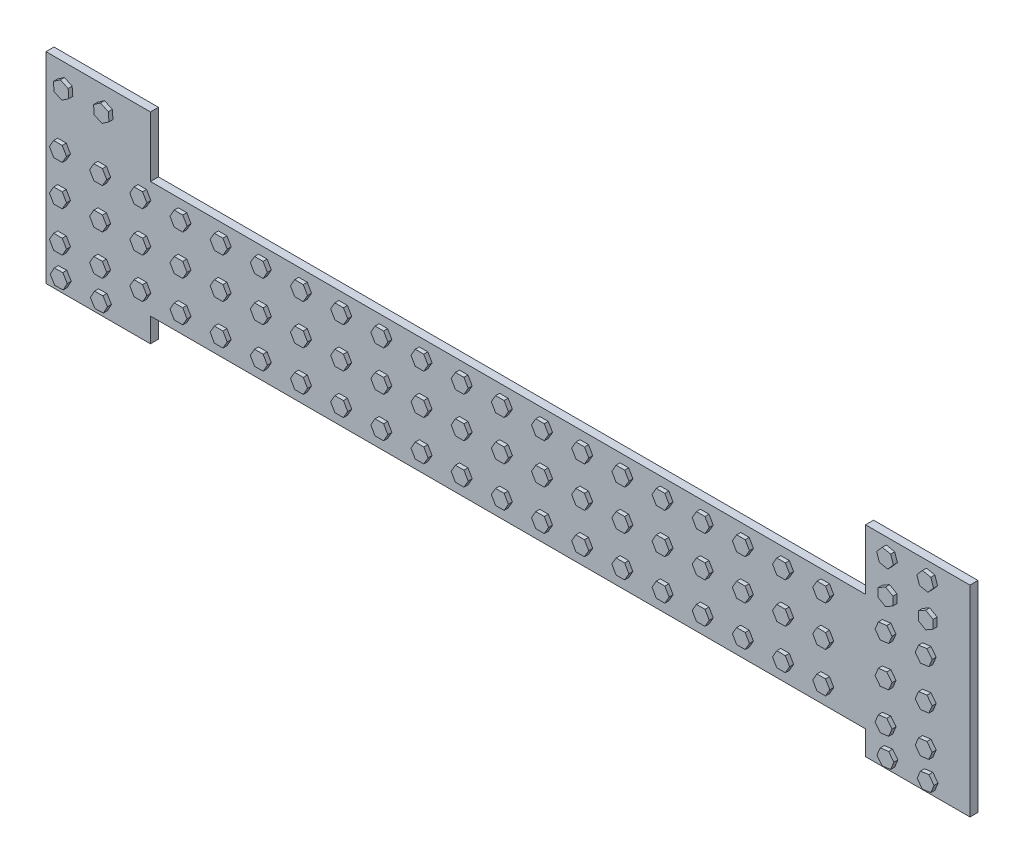
SolidWorks part; units mm, degrees
ref_plane "Front Plane" through (0, 0, 0) normal (0, 0, 1) x (1, 0, 0)
ref_plane "Top Plane" through (0, 0, 0) normal (0, 1, 0) x (1, 0, 0)
ref_plane "Right Plane" through (0, 0, 0) normal (1, 0, 0) x (0, 0, -1)
sketch "Sketch1" plane through (0, 0, 0) normal (0, 0, 1) x (1, 0, 0)
  line L0 (-145.1185, -8.2618) -> (-119.1185, -8.2618)
  line L4 (58.8815, -8.2618) -> (84.8815, -8.2618)
  line L5 (84.8815, -8.2618) -> (84.8815, 41.7382)
  line L7 (-145.1185, 41.7382) -> (-145.1185, -8.2618)
  line L8 (-119.1185, -8.2618) -> (-119.1185, -2.2618)
  line L9 (-119.1185, -2.2618) -> (58.8815, -2.2618)
  line L10 (58.8815, -2.2618) -> (58.8815, -8.2618)
  line L11 (-145.1185, 41.7382) -> (-119.1185, 41.7382)
  line L12 (-119.1185, 41.7382) -> (-119.1185, 26.7382)
  line L13 (-119.1185, 26.7382) -> (58.8815, 26.7382)
  line L14 (58.8815, 26.7382) -> (58.8815, 41.7382)
  line L15 (58.8815, 41.7382) -> (84.8815, 41.7382)
  dimension "D1" = 230
  dimension "D2" = 26
  dimension "D3" = 6
  dimension "D4" = 50
  dimension "D5" = 15
extrude "Boss-Extrude1" add sketch "Sketch1" along normal blind 3
sketch "Sketch2" plane through (0, 0, 3) normal (0, 0, 1) x (1, 0, 0)
  line L0 (-130.1882, 34.2187) -> (-128.4427, 35.4302)
  line L1 (-140.1882, 34.2187) -> (-138.4427, 35.4302)
  line L2 (-138.4427, 35.4302) -> (-138.6192, 37.5475)
  line L3 (-138.6192, 37.5475) -> (-140.541, 38.4533)
  line L4 (-140.541, 38.4533) -> (-142.2865, 37.2419)
  line L5 (-142.2865, 37.2419) -> (-142.11, 35.1246)
  line L6 (-142.11, 35.1246) -> (-140.1882, 34.2187)
  line L13 (-139.8304, -6.4856) -> (-138.8246, -4.6141)
  line L14 (-138.8246, -4.6141) -> (-139.9425, -2.8073)
  line L15 (-139.9425, -2.8073) -> (-142.0662, -2.872)
  line L16 (-142.0662, -2.872) -> (-143.072, -4.7435)
  line L17 (-143.072, -4.7435) -> (-141.9541, -6.5503)
  line L18 (-141.9541, -6.5503) -> (-139.8304, -6.4856)
  line L19 (-139.0172, 2.7003) -> (-140.0796, 4.5403)
  line L20 (-140.0796, 4.5403) -> (-142.2042, 4.5403)
  line L21 (-142.2042, 4.5403) -> (-143.2665, 2.7003)
  line L22 (-143.2665, 2.7003) -> (-142.2042, 0.8603)
  line L23 (-142.2042, 0.8603) -> (-140.0796, 0.8603)
  line L24 (-140.0796, 0.8603) -> (-139.0172, 2.7003)
  line L25 (66.1321, -6.8908) -> (66.939, -4.9253)
  line L26 (66.939, -4.9253) -> (65.6403, -3.2438)
  line L27 (65.6403, -3.2438) -> (63.5347, -3.5277)
  line L28 (63.5347, -3.5277) -> (62.7278, -5.4932)
  line L29 (62.7278, -5.4932) -> (64.0265, -7.1747)
  line L30 (64.0265, -7.1747) -> (66.1321, -6.8908)
  line L31 (65.6558, 0.0237) -> (66.4709, 1.9858)
  line L32 (66.4709, 1.9858) -> (65.1792, 3.6727)
  line L33 (65.1792, 3.6727) -> (63.0724, 3.3976)
  line L34 (63.0724, 3.3976) -> (62.2573, 1.4355)
  line L35 (62.2573, 1.4355) -> (63.549, -0.2515)
  line L36 (63.549, -0.2515) -> (65.6558, 0.0237)
  line L37 (65.4081, 35.9472) -> (66.8177, 37.5368)
  line L38 (66.8177, 37.5368) -> (66.1458, 39.5524)
  line L39 (66.1458, 39.5524) -> (64.0643, 39.9784)
  line L40 (64.0643, 39.9784) -> (62.6547, 38.3887)
  line L41 (62.6547, 38.3887) -> (63.3266, 36.3731)
  line L42 (63.3266, 36.3731) -> (65.4081, 35.9472)
  line L43 (64.8685, 27.5796) -> (66.7085, 28.6419)
  line L44 (66.7085, 28.6419) -> (66.7085, 30.7665)
  line L45 (66.7085, 30.7665) -> (64.8685, 31.8289)
  line L46 (64.8685, 31.8289) -> (63.0285, 30.7665)
  line L47 (63.0285, 30.7665) -> (63.0285, 28.6419)
  line L48 (63.0285, 28.6419) -> (64.8685, 27.5796)
  line L49 (-128.4427, 35.4302) -> (-128.6192, 37.5475)
  line L50 (-128.6192, 37.5475) -> (-130.541, 38.4533)
  line L51 (-130.541, 38.4533) -> (-132.2865, 37.2419)
  line L52 (-132.2865, 37.2419) -> (-132.11, 35.1246)
  line L53 (-132.11, 35.1246) -> (-130.1882, 34.2187)
  line L60 (-129.8304, -6.4856) -> (-128.8246, -4.6141)
  line L61 (-128.8246, -4.6141) -> (-129.9425, -2.8073)
  line L62 (-129.9425, -2.8073) -> (-132.0662, -2.872)
  line L63 (-132.0662, -2.872) -> (-133.072, -4.7435)
  line L64 (-133.072, -4.7435) -> (-131.9541, -6.5503)
  line L65 (-131.9541, -6.5503) -> (-129.8304, -6.4856)
  line L66 (76.1321, -6.8908) -> (76.939, -4.9253)
  line L67 (76.939, -4.9253) -> (75.6403, -3.2438)
  line L68 (75.6403, -3.2438) -> (73.5347, -3.5277)
  line L69 (73.5347, -3.5277) -> (72.7278, -5.4932)
  line L70 (72.7278, -5.4932) -> (74.0265, -7.1747)
  line L71 (74.0265, -7.1747) -> (76.1321, -6.8908)
  line L72 (75.6558, 0.0237) -> (76.4709, 1.9858)
  line L73 (76.4709, 1.9858) -> (75.1792, 3.6727)
  line L74 (75.1792, 3.6727) -> (73.0724, 3.3976)
  line L75 (73.0724, 3.3976) -> (72.2573, 1.4355)
  line L76 (72.2573, 1.4355) -> (73.549, -0.2515)
  line L77 (73.549, -0.2515) -> (75.6558, 0.0237)
  line L78 (75.4081, 35.9472) -> (76.8177, 37.5368)
  line L79 (76.8177, 37.5368) -> (76.1458, 39.5524)
  line L80 (76.1458, 39.5524) -> (74.0643, 39.9784)
  line L81 (74.0643, 39.9784) -> (72.6547, 38.3887)
  line L82 (72.6547, 38.3887) -> (73.3266, 36.3731)
  line L83 (73.3266, 36.3731) -> (75.4081, 35.9472)
  line L84 (74.8685, 27.5796) -> (76.7085, 28.6419)
  line L85 (76.7085, 28.6419) -> (76.7085, 30.7665)
  line L86 (76.7085, 30.7665) -> (74.8685, 31.8289)
  line L87 (74.8685, 31.8289) -> (73.0285, 30.7665)
  line L88 (73.0285, 30.7665) -> (73.0285, 28.6419)
  line L89 (73.0285, 28.6419) -> (74.8685, 27.5796)
  line L90 (-129.0172, 2.7003) -> (-130.0796, 4.5403)
  line L91 (-130.0796, 4.5403) -> (-132.2042, 4.5403)
  line L92 (-132.2042, 4.5403) -> (-133.2665, 2.7003)
  line L93 (-133.2665, 2.7003) -> (-132.2042, 0.8603)
  line L94 (-132.2042, 0.8603) -> (-130.0796, 0.8603)
  line L95 (-130.0796, 0.8603) -> (-129.0172, 2.7003)
  line L96 (-119.0172, 2.7003) -> (-120.0796, 4.5403)
  line L97 (-120.0796, 4.5403) -> (-122.2042, 4.5403)
  line L98 (-122.2042, 4.5403) -> (-123.2665, 2.7003)
  line L99 (-123.2665, 2.7003) -> (-122.2042, 0.8603)
  line L100 (-122.2042, 0.8603) -> (-120.0796, 0.8603)
  line L101 (-120.0796, 0.8603) -> (-119.0172, 2.7003)
  line L102 (-109.0172, 2.7003) -> (-110.0796, 4.5403)
  line L103 (-110.0796, 4.5403) -> (-112.2042, 4.5403)
  line L104 (-112.2042, 4.5403) -> (-113.2665, 2.7003)
  line L105 (-113.2665, 2.7003) -> (-112.2042, 0.8603)
  line L106 (-112.2042, 0.8603) -> (-110.0796, 0.8603)
  line L107 (-110.0796, 0.8603) -> (-109.0172, 2.7003)
  line L108 (-99.0172, 2.7003) -> (-100.0796, 4.5403)
  line L109 (-100.0796, 4.5403) -> (-102.2042, 4.5403)
  line L110 (-102.2042, 4.5403) -> (-103.2665, 2.7003)
  line L111 (-103.2665, 2.7003) -> (-102.2042, 0.8603)
  line L112 (-102.2042, 0.8603) -> (-100.0796, 0.8603)
  line L113 (-100.0796, 0.8603) -> (-99.0172, 2.7003)
  line L114 (-89.0172, 2.7003) -> (-90.0796, 4.5403)
  line L115 (-90.0796, 4.5403) -> (-92.2042, 4.5403)
  line L116 (-92.2042, 4.5403) -> (-93.2665, 2.7003)
  line L117 (-93.2665, 2.7003) -> (-92.2042, 0.8603)
  line L118 (-92.2042, 0.8603) -> (-90.0796, 0.8603)
  line L119 (-90.0796, 0.8603) -> (-89.0172, 2.7003)
  line L120 (-79.0172, 2.7003) -> (-80.0796, 4.5403)
  line L121 (-80.0796, 4.5403) -> (-82.2042, 4.5403)
  line L122 (-82.2042, 4.5403) -> (-83.2665, 2.7003)
  line L123 (-83.2665, 2.7003) -> (-82.2042, 0.8603)
  line L124 (-82.2042, 0.8603) -> (-80.0796, 0.8603)
  line L125 (-80.0796, 0.8603) -> (-79.0172, 2.7003)
  line L126 (-69.0172, 2.7003) -> (-70.0796, 4.5403)
  line L127 (-70.0796, 4.5403) -> (-72.2042, 4.5403)
  line L128 (-72.2042, 4.5403) -> (-73.2665, 2.7003)
  line L129 (-73.2665, 2.7003) -> (-72.2042, 0.8603)
  line L130 (-72.2042, 0.8603) -> (-70.0796, 0.8603)
  line L131 (-70.0796, 0.8603) -> (-69.0172, 2.7003)
  line L132 (-59.0172, 2.7003) -> (-60.0796, 4.5403)
  line L133 (-60.0796, 4.5403) -> (-62.2042, 4.5403)
  line L134 (-62.2042, 4.5403) -> (-63.2665, 2.7003)
  line L135 (-63.2665, 2.7003) -> (-62.2042, 0.8603)
  line L136 (-62.2042, 0.8603) -> (-60.0796, 0.8603)
  line L137 (-60.0796, 0.8603) -> (-59.0172, 2.7003)
  line L138 (-49.0172, 2.7003) -> (-50.0796, 4.5403)
  line L139 (-50.0796, 4.5403) -> (-52.2042, 4.5403)
  line L140 (-52.2042, 4.5403) -> (-53.2665, 2.7003)
  line L141 (-53.2665, 2.7003) -> (-52.2042, 0.8603)
  line L142 (-52.2042, 0.8603) -> (-50.0796, 0.8603)
  line L143 (-50.0796, 0.8603) -> (-49.0172, 2.7003)
  line L144 (-39.0172, 2.7003) -> (-40.0796, 4.5403)
  line L145 (-40.0796, 4.5403) -> (-42.2042, 4.5403)
  line L146 (-42.2042, 4.5403) -> (-43.2665, 2.7003)
  line L147 (-43.2665, 2.7003) -> (-42.2042, 0.8603)
  line L148 (-42.2042, 0.8603) -> (-40.0796, 0.8603)
  line L149 (-40.0796, 0.8603) -> (-39.0172, 2.7003)
  line L150 (-29.0172, 2.7003) -> (-30.0796, 4.5403)
  line L151 (-30.0796, 4.5403) -> (-32.2042, 4.5403)
  line L152 (-32.2042, 4.5403) -> (-33.2665, 2.7003)
  line L153 (-33.2665, 2.7003) -> (-32.2042, 0.8603)
  line L154 (-32.2042, 0.8603) -> (-30.0796, 0.8603)
  line L155 (-30.0796, 0.8603) -> (-29.0172, 2.7003)
  line L156 (-19.0172, 2.7003) -> (-20.0796, 4.5403)
  line L157 (-20.0796, 4.5403) -> (-22.2042, 4.5403)
  line L158 (-22.2042, 4.5403) -> (-23.2665, 2.7003)
  line L159 (-23.2665, 2.7003) -> (-22.2042, 0.8603)
  line L160 (-22.2042, 0.8603) -> (-20.0796, 0.8603)
  line L161 (-20.0796, 0.8603) -> (-19.0172, 2.7003)
  line L162 (-9.0172, 2.7003) -> (-10.0796, 4.5403)
  line L163 (-10.0796, 4.5403) -> (-12.2042, 4.5403)
  line L164 (-12.2042, 4.5403) -> (-13.2665, 2.7003)
  line L165 (-13.2665, 2.7003) -> (-12.2042, 0.8603)
  line L166 (-12.2042, 0.8603) -> (-10.0796, 0.8603)
  line L167 (-10.0796, 0.8603) -> (-9.0172, 2.7003)
  line L168 (0.9828, 2.7003) -> (-0.0796, 4.5403)
  line L169 (-0.0796, 4.5403) -> (-2.2042, 4.5403)
  line L170 (-2.2042, 4.5403) -> (-3.2665, 2.7003)
  line L171 (-3.2665, 2.7003) -> (-2.2042, 0.8603)
  line L172 (-2.2042, 0.8603) -> (-0.0796, 0.8603)
  line L173 (-0.0796, 0.8603) -> (0.9828, 2.7003)
  line L174 (10.9828, 2.7003) -> (9.9204, 4.5403)
  line L175 (9.9204, 4.5403) -> (7.7958, 4.5403)
  line L176 (7.7958, 4.5403) -> (6.7335, 2.7003)
  line L177 (6.7335, 2.7003) -> (7.7958, 0.8603)
  line L178 (7.7958, 0.8603) -> (9.9204, 0.8603)
  line L179 (9.9204, 0.8603) -> (10.9828, 2.7003)
  line L180 (20.9828, 2.7003) -> (19.9204, 4.5403)
  line L181 (19.9204, 4.5403) -> (17.7958, 4.5403)
  line L182 (17.7958, 4.5403) -> (16.7335, 2.7003)
  line L183 (16.7335, 2.7003) -> (17.7958, 0.8603)
  line L184 (17.7958, 0.8603) -> (19.9204, 0.8603)
  line L185 (19.9204, 0.8603) -> (20.9828, 2.7003)
  line L186 (30.9828, 2.7003) -> (29.9204, 4.5403)
  line L187 (29.9204, 4.5403) -> (27.7958, 4.5403)
  line L188 (27.7958, 4.5403) -> (26.7335, 2.7003)
  line L189 (26.7335, 2.7003) -> (27.7958, 0.8603)
  line L190 (27.7958, 0.8603) -> (29.9204, 0.8603)
  line L191 (29.9204, 0.8603) -> (30.9828, 2.7003)
  line L192 (40.9828, 2.7003) -> (39.9204, 4.5403)
  line L193 (39.9204, 4.5403) -> (37.7958, 4.5403)
  line L194 (37.7958, 4.5403) -> (36.7335, 2.7003)
  line L195 (36.7335, 2.7003) -> (37.7958, 0.8603)
  line L196 (37.7958, 0.8603) -> (39.9204, 0.8603)
  line L197 (39.9204, 0.8603) -> (40.9828, 2.7003)
  line L198 (50.9828, 2.7003) -> (49.9204, 4.5403)
  line L199 (49.9204, 4.5403) -> (47.7958, 4.5403)
  line L200 (47.7958, 4.5403) -> (46.7335, 2.7003)
  line L201 (46.7335, 2.7003) -> (47.7958, 0.8603)
  line L202 (47.7958, 0.8603) -> (49.9204, 0.8603)
  line L203 (49.9204, 0.8603) -> (50.9828, 2.7003)
  line L204 (-129.0172, 12.7003) -> (-130.0796, 14.5403)
  line L205 (-130.0796, 14.5403) -> (-132.2042, 14.5403)
  line L206 (-132.2042, 14.5403) -> (-133.2665, 12.7003)
  line L207 (-133.2665, 12.7003) -> (-132.2042, 10.8603)
  line L208 (-132.2042, 10.8603) -> (-130.0796, 10.8603)
  line L209 (-130.0796, 10.8603) -> (-129.0172, 12.7003)
  line L210 (-119.0172, 12.7003) -> (-120.0796, 14.5403)
  line L211 (-120.0796, 14.5403) -> (-122.2042, 14.5403)
  line L212 (-122.2042, 14.5403) -> (-123.2665, 12.7003)
  line L213 (-123.2665, 12.7003) -> (-122.2042, 10.8603)
  line L214 (-122.2042, 10.8603) -> (-120.0796, 10.8603)
  line L215 (-120.0796, 10.8603) -> (-119.0172, 12.7003)
  line L216 (-109.0172, 12.7003) -> (-110.0796, 14.5403)
  line L217 (-110.0796, 14.5403) -> (-112.2042, 14.5403)
  line L218 (-112.2042, 14.5403) -> (-113.2665, 12.7003)
  line L219 (-113.2665, 12.7003) -> (-112.2042, 10.8603)
  line L220 (-112.2042, 10.8603) -> (-110.0796, 10.8603)
  line L221 (-110.0796, 10.8603) -> (-109.0172, 12.7003)
  line L222 (-99.0172, 12.7003) -> (-100.0796, 14.5403)
  line L223 (-100.0796, 14.5403) -> (-102.2042, 14.5403)
  line L224 (-102.2042, 14.5403) -> (-103.2665, 12.7003)
  line L225 (-103.2665, 12.7003) -> (-102.2042, 10.8603)
  line L226 (-102.2042, 10.8603) -> (-100.0796, 10.8603)
  line L227 (-100.0796, 10.8603) -> (-99.0172, 12.7003)
  line L228 (-89.0172, 12.7003) -> (-90.0796, 14.5403)
  line L229 (-90.0796, 14.5403) -> (-92.2042, 14.5403)
  line L230 (-92.2042, 14.5403) -> (-93.2665, 12.7003)
  line L231 (-93.2665, 12.7003) -> (-92.2042, 10.8603)
  line L232 (-92.2042, 10.8603) -> (-90.0796, 10.8603)
  line L233 (-90.0796, 10.8603) -> (-89.0172, 12.7003)
  line L234 (-79.0172, 12.7003) -> (-80.0796, 14.5403)
  line L235 (-80.0796, 14.5403) -> (-82.2042, 14.5403)
  line L236 (-82.2042, 14.5403) -> (-83.2665, 12.7003)
  line L237 (-83.2665, 12.7003) -> (-82.2042, 10.8603)
  line L238 (-82.2042, 10.8603) -> (-80.0796, 10.8603)
  line L239 (-80.0796, 10.8603) -> (-79.0172, 12.7003)
  line L240 (-69.0172, 12.7003) -> (-70.0796, 14.5403)
  line L241 (-70.0796, 14.5403) -> (-72.2042, 14.5403)
  line L242 (-72.2042, 14.5403) -> (-73.2665, 12.7003)
  line L243 (-73.2665, 12.7003) -> (-72.2042, 10.8603)
  line L244 (-72.2042, 10.8603) -> (-70.0796, 10.8603)
  line L245 (-70.0796, 10.8603) -> (-69.0172, 12.7003)
  line L246 (-59.0172, 12.7003) -> (-60.0796, 14.5403)
  line L247 (-60.0796, 14.5403) -> (-62.2042, 14.5403)
  line L248 (-62.2042, 14.5403) -> (-63.2665, 12.7003)
  line L249 (-63.2665, 12.7003) -> (-62.2042, 10.8603)
  line L250 (-62.2042, 10.8603) -> (-60.0796, 10.8603)
  line L251 (-60.0796, 10.8603) -> (-59.0172, 12.7003)
  line L252 (-49.0172, 12.7003) -> (-50.0796, 14.5403)
  line L253 (-50.0796, 14.5403) -> (-52.2042, 14.5403)
  line L254 (-52.2042, 14.5403) -> (-53.2665, 12.7003)
  line L255 (-53.2665, 12.7003) -> (-52.2042, 10.8603)
  line L256 (-52.2042, 10.8603) -> (-50.0796, 10.8603)
  line L257 (-50.0796, 10.8603) -> (-49.0172, 12.7003)
  line L258 (-39.0172, 12.7003) -> (-40.0796, 14.5403)
  line L259 (-40.0796, 14.5403) -> (-42.2042, 14.5403)
  line L260 (-42.2042, 14.5403) -> (-43.2665, 12.7003)
  line L261 (-43.2665, 12.7003) -> (-42.2042, 10.8603)
  line L262 (-42.2042, 10.8603) -> (-40.0796, 10.8603)
  line L263 (-40.0796, 10.8603) -> (-39.0172, 12.7003)
  line L264 (-29.0172, 12.7003) -> (-30.0796, 14.5403)
  line L265 (-30.0796, 14.5403) -> (-32.2042, 14.5403)
  line L266 (-32.2042, 14.5403) -> (-33.2665, 12.7003)
  line L267 (-33.2665, 12.7003) -> (-32.2042, 10.8603)
  line L268 (-32.2042, 10.8603) -> (-30.0796, 10.8603)
  line L269 (-30.0796, 10.8603) -> (-29.0172, 12.7003)
  line L270 (-19.0172, 12.7003) -> (-20.0796, 14.5403)
  line L271 (-20.0796, 14.5403) -> (-22.2042, 14.5403)
  line L272 (-22.2042, 14.5403) -> (-23.2665, 12.7003)
  line L273 (-23.2665, 12.7003) -> (-22.2042, 10.8603)
  line L274 (-22.2042, 10.8603) -> (-20.0796, 10.8603)
  line L275 (-20.0796, 10.8603) -> (-19.0172, 12.7003)
  line L276 (-9.0172, 12.7003) -> (-10.0796, 14.5403)
  line L277 (-10.0796, 14.5403) -> (-12.2042, 14.5403)
  line L278 (-12.2042, 14.5403) -> (-13.2665, 12.7003)
  line L279 (-13.2665, 12.7003) -> (-12.2042, 10.8603)
  line L280 (-12.2042, 10.8603) -> (-10.0796, 10.8603)
  line L281 (-10.0796, 10.8603) -> (-9.0172, 12.7003)
  line L282 (0.9828, 12.7003) -> (-0.0796, 14.5403)
  line L283 (-0.0796, 14.5403) -> (-2.2042, 14.5403)
  line L284 (-2.2042, 14.5403) -> (-3.2665, 12.7003)
  line L285 (-3.2665, 12.7003) -> (-2.2042, 10.8603)
  line L286 (-2.2042, 10.8603) -> (-0.0796, 10.8603)
  line L287 (-0.0796, 10.8603) -> (0.9828, 12.7003)
  line L288 (10.9828, 12.7003) -> (9.9204, 14.5403)
  line L289 (9.9204, 14.5403) -> (7.7958, 14.5403)
  line L290 (7.7958, 14.5403) -> (6.7335, 12.7003)
  line L291 (6.7335, 12.7003) -> (7.7958, 10.8603)
  line L292 (7.7958, 10.8603) -> (9.9204, 10.8603)
  line L293 (9.9204, 10.8603) -> (10.9828, 12.7003)
  line L294 (20.9828, 12.7003) -> (19.9204, 14.5403)
  line L295 (19.9204, 14.5403) -> (17.7958, 14.5403)
  line L296 (17.7958, 14.5403) -> (16.7335, 12.7003)
  line L297 (16.7335, 12.7003) -> (17.7958, 10.8603)
  line L298 (17.7958, 10.8603) -> (19.9204, 10.8603)
  line L299 (19.9204, 10.8603) -> (20.9828, 12.7003)
  line L300 (30.9828, 12.7003) -> (29.9204, 14.5403)
  line L301 (29.9204, 14.5403) -> (27.7958, 14.5403)
  line L302 (27.7958, 14.5403) -> (26.7335, 12.7003)
  line L303 (26.7335, 12.7003) -> (27.7958, 10.8603)
  line L304 (27.7958, 10.8603) -> (29.9204, 10.8603)
  line L305 (29.9204, 10.8603) -> (30.9828, 12.7003)
  line L306 (40.9828, 12.7003) -> (39.9204, 14.5403)
  line L307 (39.9204, 14.5403) -> (37.7958, 14.5403)
  line L308 (37.7958, 14.5403) -> (36.7335, 12.7003)
  line L309 (36.7335, 12.7003) -> (37.7958, 10.8603)
  line L310 (37.7958, 10.8603) -> (39.9204, 10.8603)
  line L311 (39.9204, 10.8603) -> (40.9828, 12.7003)
  line L312 (50.9828, 12.7003) -> (49.9204, 14.5403)
  line L313 (49.9204, 14.5403) -> (47.7958, 14.5403)
  line L314 (47.7958, 14.5403) -> (46.7335, 12.7003)
  line L315 (46.7335, 12.7003) -> (47.7958, 10.8603)
  line L316 (47.7958, 10.8603) -> (49.9204, 10.8603)
  line L317 (49.9204, 10.8603) -> (50.9828, 12.7003)
  line L318 (-129.0172, 22.7003) -> (-130.0796, 24.5403)
  line L319 (-130.0796, 24.5403) -> (-132.2042, 24.5403)
  line L320 (-132.2042, 24.5403) -> (-133.2665, 22.7003)
  line L321 (-133.2665, 22.7003) -> (-132.2042, 20.8603)
  line L322 (-132.2042, 20.8603) -> (-130.0796, 20.8603)
  line L323 (-130.0796, 20.8603) -> (-129.0172, 22.7003)
  line L324 (-119.0172, 22.7003) -> (-120.0796, 24.5403)
  line L325 (-120.0796, 24.5403) -> (-122.2042, 24.5403)
  line L326 (-122.2042, 24.5403) -> (-123.2665, 22.7003)
  line L327 (-123.2665, 22.7003) -> (-122.2042, 20.8603)
  line L328 (-122.2042, 20.8603) -> (-120.0796, 20.8603)
  line L329 (-120.0796, 20.8603) -> (-119.0172, 22.7003)
  line L330 (-109.0172, 22.7003) -> (-110.0796, 24.5403)
  line L331 (-110.0796, 24.5403) -> (-112.2042, 24.5403)
  line L332 (-112.2042, 24.5403) -> (-113.2665, 22.7003)
  line L333 (-113.2665, 22.7003) -> (-112.2042, 20.8603)
  line L334 (-112.2042, 20.8603) -> (-110.0796, 20.8603)
  line L335 (-110.0796, 20.8603) -> (-109.0172, 22.7003)
  line L336 (-99.0172, 22.7003) -> (-100.0796, 24.5403)
  line L337 (-100.0796, 24.5403) -> (-102.2042, 24.5403)
  line L338 (-102.2042, 24.5403) -> (-103.2665, 22.7003)
  line L339 (-103.2665, 22.7003) -> (-102.2042, 20.8603)
  line L340 (-102.2042, 20.8603) -> (-100.0796, 20.8603)
  line L341 (-100.0796, 20.8603) -> (-99.0172, 22.7003)
  line L342 (-89.0172, 22.7003) -> (-90.0796, 24.5403)
  line L343 (-90.0796, 24.5403) -> (-92.2042, 24.5403)
  line L344 (-92.2042, 24.5403) -> (-93.2665, 22.7003)
  line L345 (-93.2665, 22.7003) -> (-92.2042, 20.8603)
  line L346 (-92.2042, 20.8603) -> (-90.0796, 20.8603)
  line L347 (-90.0796, 20.8603) -> (-89.0172, 22.7003)
  line L348 (-79.0172, 22.7003) -> (-80.0796, 24.5403)
  line L349 (-80.0796, 24.5403) -> (-82.2042, 24.5403)
  line L350 (-82.2042, 24.5403) -> (-83.2665, 22.7003)
  line L351 (-83.2665, 22.7003) -> (-82.2042, 20.8603)
  line L352 (-82.2042, 20.8603) -> (-80.0796, 20.8603)
  line L353 (-80.0796, 20.8603) -> (-79.0172, 22.7003)
  line L354 (-69.0172, 22.7003) -> (-70.0796, 24.5403)
  line L355 (-70.0796, 24.5403) -> (-72.2042, 24.5403)
  line L356 (-72.2042, 24.5403) -> (-73.2665, 22.7003)
  line L357 (-73.2665, 22.7003) -> (-72.2042, 20.8603)
  line L358 (-72.2042, 20.8603) -> (-70.0796, 20.8603)
  line L359 (-70.0796, 20.8603) -> (-69.0172, 22.7003)
  line L360 (-59.0172, 22.7003) -> (-60.0796, 24.5403)
  line L361 (-60.0796, 24.5403) -> (-62.2042, 24.5403)
  line L362 (-62.2042, 24.5403) -> (-63.2665, 22.7003)
  line L363 (-63.2665, 22.7003) -> (-62.2042, 20.8603)
  line L364 (-62.2042, 20.8603) -> (-60.0796, 20.8603)
  line L365 (-60.0796, 20.8603) -> (-59.0172, 22.7003)
  line L366 (-49.0172, 22.7003) -> (-50.0796, 24.5403)
  line L367 (-50.0796, 24.5403) -> (-52.2042, 24.5403)
  line L368 (-52.2042, 24.5403) -> (-53.2665, 22.7003)
  line L369 (-53.2665, 22.7003) -> (-52.2042, 20.8603)
  line L370 (-52.2042, 20.8603) -> (-50.0796, 20.8603)
  line L371 (-50.0796, 20.8603) -> (-49.0172, 22.7003)
  line L372 (-39.0172, 22.7003) -> (-40.0796, 24.5403)
  line L373 (-40.0796, 24.5403) -> (-42.2042, 24.5403)
  line L374 (-42.2042, 24.5403) -> (-43.2665, 22.7003)
  line L375 (-43.2665, 22.7003) -> (-42.2042, 20.8603)
  line L376 (-42.2042, 20.8603) -> (-40.0796, 20.8603)
  line L377 (-40.0796, 20.8603) -> (-39.0172, 22.7003)
  line L378 (-29.0172, 22.7003) -> (-30.0796, 24.5403)
  line L379 (-30.0796, 24.5403) -> (-32.2042, 24.5403)
  line L380 (-32.2042, 24.5403) -> (-33.2665, 22.7003)
  line L381 (-33.2665, 22.7003) -> (-32.2042, 20.8603)
  line L382 (-32.2042, 20.8603) -> (-30.0796, 20.8603)
  line L383 (-30.0796, 20.8603) -> (-29.0172, 22.7003)
  line L384 (-19.0172, 22.7003) -> (-20.0796, 24.5403)
  line L385 (-20.0796, 24.5403) -> (-22.2042, 24.5403)
  line L386 (-22.2042, 24.5403) -> (-23.2665, 22.7003)
  line L387 (-23.2665, 22.7003) -> (-22.2042, 20.8603)
  line L388 (-22.2042, 20.8603) -> (-20.0796, 20.8603)
  line L389 (-20.0796, 20.8603) -> (-19.0172, 22.7003)
  line L390 (-9.0172, 22.7003) -> (-10.0796, 24.5403)
  line L391 (-10.0796, 24.5403) -> (-12.2042, 24.5403)
  line L392 (-12.2042, 24.5403) -> (-13.2665, 22.7003)
  line L393 (-13.2665, 22.7003) -> (-12.2042, 20.8603)
  line L394 (-12.2042, 20.8603) -> (-10.0796, 20.8603)
  line L395 (-10.0796, 20.8603) -> (-9.0172, 22.7003)
  line L396 (0.9828, 22.7003) -> (-0.0796, 24.5403)
  line L397 (-0.0796, 24.5403) -> (-2.2042, 24.5403)
  line L398 (-2.2042, 24.5403) -> (-3.2665, 22.7003)
  line L399 (-3.2665, 22.7003) -> (-2.2042, 20.8603)
  line L400 (-2.2042, 20.8603) -> (-0.0796, 20.8603)
  line L401 (-0.0796, 20.8603) -> (0.9828, 22.7003)
  line L402 (10.9828, 22.7003) -> (9.9204, 24.5403)
  line L403 (9.9204, 24.5403) -> (7.7958, 24.5403)
  line L404 (7.7958, 24.5403) -> (6.7335, 22.7003)
  line L405 (6.7335, 22.7003) -> (7.7958, 20.8603)
  line L406 (7.7958, 20.8603) -> (9.9204, 20.8603)
  line L407 (9.9204, 20.8603) -> (10.9828, 22.7003)
  line L408 (20.9828, 22.7003) -> (19.9204, 24.5403)
  line L409 (19.9204, 24.5403) -> (17.7958, 24.5403)
  line L410 (17.7958, 24.5403) -> (16.7335, 22.7003)
  line L411 (16.7335, 22.7003) -> (17.7958, 20.8603)
  line L412 (17.7958, 20.8603) -> (19.9204, 20.8603)
  line L413 (19.9204, 20.8603) -> (20.9828, 22.7003)
  line L414 (30.9828, 22.7003) -> (29.9204, 24.5403)
  line L415 (29.9204, 24.5403) -> (27.7958, 24.5403)
  line L416 (27.7958, 24.5403) -> (26.7335, 22.7003)
  line L417 (26.7335, 22.7003) -> (27.7958, 20.8603)
  line L418 (27.7958, 20.8603) -> (29.9204, 20.8603)
  line L419 (29.9204, 20.8603) -> (30.9828, 22.7003)
  line L420 (40.9828, 22.7003) -> (39.9204, 24.5403)
  line L421 (39.9204, 24.5403) -> (37.7958, 24.5403)
  line L422 (37.7958, 24.5403) -> (36.7335, 22.7003)
  line L423 (36.7335, 22.7003) -> (37.7958, 20.8603)
  line L424 (37.7958, 20.8603) -> (39.9204, 20.8603)
  line L425 (39.9204, 20.8603) -> (40.9828, 22.7003)
  line L426 (50.9828, 22.7003) -> (49.9204, 24.5403)
  line L427 (49.9204, 24.5403) -> (47.7958, 24.5403)
  line L428 (47.7958, 24.5403) -> (46.7335, 22.7003)
  line L429 (46.7335, 22.7003) -> (47.7958, 20.8603)
  line L430 (47.7958, 20.8603) -> (49.9204, 20.8603)
  line L431 (49.9204, 20.8603) -> (50.9828, 22.7003)
  line L432 (-139.0172, 12.7003) -> (-140.0796, 14.5403)
  line L433 (-140.0796, 14.5403) -> (-142.2042, 14.5403)
  line L434 (-142.2042, 14.5403) -> (-143.2665, 12.7003)
  line L435 (-143.2665, 12.7003) -> (-142.2042, 10.8603)
  line L436 (-142.2042, 10.8603) -> (-140.0796, 10.8603)
  line L437 (-140.0796, 10.8603) -> (-139.0172, 12.7003)
  line L438 (-139.0172, 22.7003) -> (-140.0796, 24.5403)
  line L439 (-140.0796, 24.5403) -> (-142.2042, 24.5403)
  line L440 (-142.2042, 24.5403) -> (-143.2665, 22.7003)
  line L441 (-143.2665, 22.7003) -> (-142.2042, 20.8603)
  line L442 (-142.2042, 20.8603) -> (-140.0796, 20.8603)
  line L443 (-140.0796, 20.8603) -> (-139.0172, 22.7003)
  line L450 (75.6558, 0.0237) -> (76.4709, 1.9858)
  line L451 (76.4709, 1.9858) -> (75.1792, 3.6727)
  line L452 (75.1792, 3.6727) -> (73.0724, 3.3976)
  line L453 (73.0724, 3.3976) -> (72.2573, 1.4355)
  line L454 (72.2573, 1.4355) -> (73.549, -0.2515)
  line L455 (73.549, -0.2515) -> (75.6558, 0.0237)
  line L456 (75.6558, 10.0237) -> (76.4709, 11.9858)
  line L457 (76.4709, 11.9858) -> (75.1792, 13.6727)
  line L458 (75.1792, 13.6727) -> (73.0724, 13.3976)
  line L459 (73.0724, 13.3976) -> (72.2573, 11.4355)
  line L460 (72.2573, 11.4355) -> (73.549, 9.7485)
  line L461 (73.549, 9.7485) -> (75.6558, 10.0237)
  line L462 (75.6558, 20.0237) -> (76.4709, 21.9858)
  line L463 (76.4709, 21.9858) -> (75.1792, 23.6727)
  line L464 (75.1792, 23.6727) -> (73.0724, 23.3976)
  line L465 (73.0724, 23.3976) -> (72.2573, 21.4355)
  line L466 (72.2573, 21.4355) -> (73.549, 19.7485)
  line L467 (73.549, 19.7485) -> (75.6558, 20.0237)
  line L468 (65.6558, 10.0237) -> (66.4709, 11.9858)
  line L469 (66.4709, 11.9858) -> (65.1792, 13.6727)
  line L470 (65.1792, 13.6727) -> (63.0724, 13.3976)
  line L471 (63.0724, 13.3976) -> (62.2573, 11.4355)
  line L472 (62.2573, 11.4355) -> (63.549, 9.7485)
  line L473 (63.549, 9.7485) -> (65.6558, 10.0237)
  line L474 (65.6558, 20.0237) -> (66.4709, 21.9858)
  line L475 (66.4709, 21.9858) -> (65.1792, 23.6727)
  line L476 (65.1792, 23.6727) -> (63.0724, 23.3976)
  line L477 (63.0724, 23.3976) -> (62.2573, 21.4355)
  line L478 (62.2573, 21.4355) -> (63.549, 19.7485)
  line L479 (63.549, 19.7485) -> (65.6558, 20.0237)
  circle A0 centre (-140.3646, 36.336) radius 1.84 construction
  circle A2 centre (-140.9483, -4.6788) radius 1.84 construction
  circle A3 centre (-141.1419, 2.7003) radius 1.84 construction
  circle A4 centre (64.8334, -5.2092) radius 1.84 construction
  circle A5 centre (64.3641, 1.7106) radius 1.84 construction
  circle A6 centre (64.7362, 37.9628) radius 1.84 construction
  circle A7 centre (64.8685, 29.7042) radius 1.84 construction
  line M445 (-145.1185, 41.7382) -> (-145.1185, -8.2618)
  line M446 (-145.1185, -8.2618) -> (-119.1185, -8.2618)
  line M447 (-119.1185, -8.2618) -> (-119.1185, -2.2618)
  line M448 (-119.1185, -2.2618) -> (58.8815, -2.2618)
  line M449 (58.8815, -2.2618) -> (58.8815, -8.2618)
  line M450 (58.8815, -8.2618) -> (84.8815, -8.2618)
  line M451 (84.8815, -8.2618) -> (84.8815, 41.7382)
  line M452 (84.8815, 41.7382) -> (58.8815, 41.7382)
  line M453 (58.8815, 41.7382) -> (58.8815, 26.7382)
  line M454 (58.8815, 26.7382) -> (-119.1185, 26.7382)
  line M455 (-119.1185, 26.7382) -> (-119.1185, 41.7382)
  line M456 (-119.1185, 41.7382) -> (-145.1185, 41.7382)
  dimension "D1" = 3.68
  dimension "D2" = 2
  dimension "D3" = 3.68
  dimension "D4" = 3.68
  dimension "D5" = 3.68
  dimension "D6" = 3.68
  dimension "D7" = 3.68
  dimension "D8" = 3.68
  dimension "D9" = 2
  dimension "D10" = 20
  dimension "D11" = 3
  dimension "D12" = 3
extrude "Cut-Extrude1" cut sketch "Sketch2" against normal blind 1 contours L479 L478 L477 L476 L475 L474 L473 L472 L471 L470 L469 L468 L467 L466 L465 L464 L463 L462 L461 L460 L459 L458 L457 L456 L443 L442 L441 L440 L439 L438 L437 L436 L435 M456 M445 M446 M447 M448 M449 M450 M451 M452 M453 M454 M455 region at (-132.1185, 39.3844, 3)
